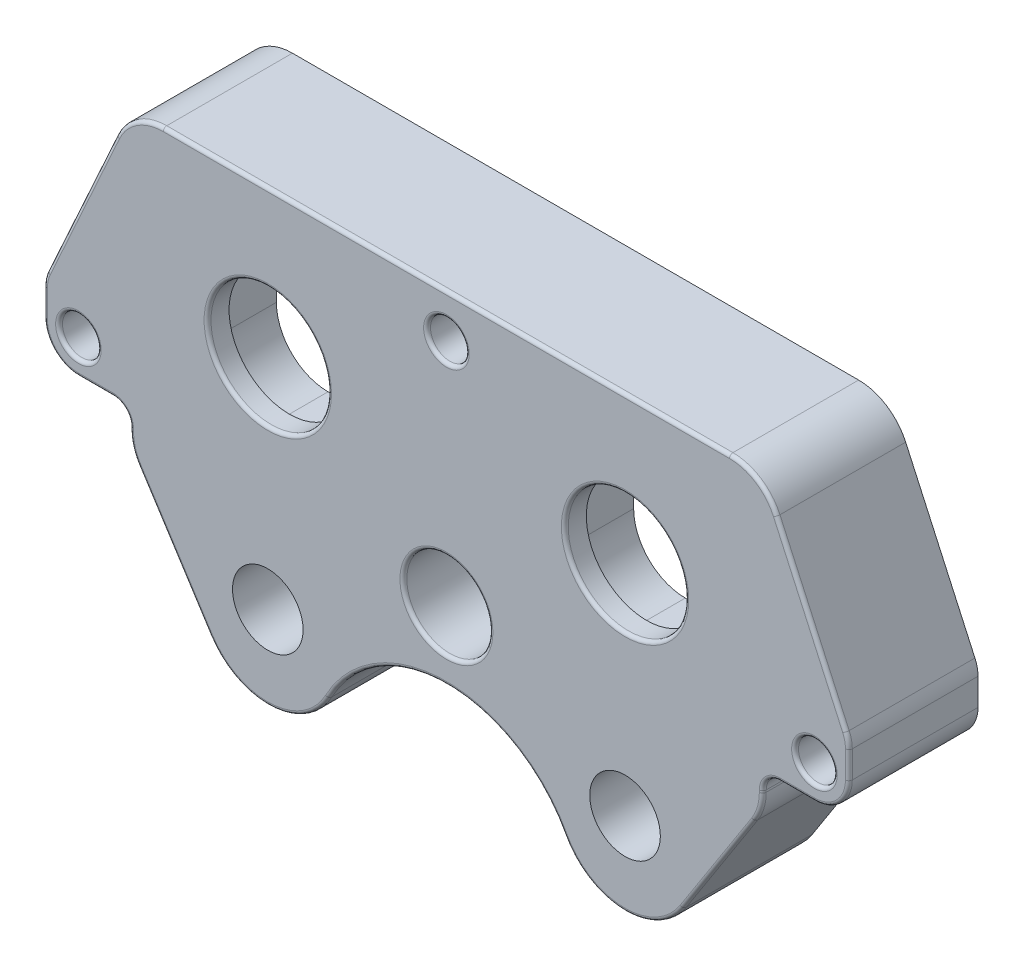
SolidWorks part; units mm, degrees
ref_plane "Front Plane" through (0, 0, 0) normal (0, 0, 1) x (1, 0, 0)
ref_plane "Top Plane" through (0, 0, 0) normal (0, 1, 0) x (1, 0, 0)
ref_plane "Right Plane" through (0, 0, 0) normal (1, 0, 0) x (0, 0, -1)
sketch "Sketch1" plane through (0, 0, 0) normal (0, 0, 1) x (1, 0, 0)
  line L0 (55.5, 15) -> (27.5, 15)
  line L1 (14, 15) -> (-14, 15)
  line L2 (14, 15) -> (14, -15)
  line L3 (14, -15) -> (-14, -15)
  line L4 (-14, 15) -> (-14, -15)
  line L5 (14, 15) -> (-14, -15) construction
  line L6 (14, -15) -> (-14, 15) construction
  line L7 (-16.75, -42) -> (16.75, -42)
  line L8 (-16.75, -42) -> (-16.75, 16)
  line L9 (-16.75, 16) -> (16.75, 16)
  line L10 (16.75, -42) -> (16.75, 16)
  line L11 (55.5, 15) -> (55.5, -15)
  line L12 (55.5, -15) -> (27.5, -15)
  line L13 (27.5, 15) -> (27.5, -15)
  line L14 (55.5, 15) -> (27.5, -15) construction
  line L15 (55.5, -15) -> (27.5, 15) construction
  line L16 (24.75, -42) -> (58.25, -42)
  line L17 (24.75, -42) -> (24.75, 16)
  line L18 (24.75, 16) -> (58.25, 16)
  line L19 (58.25, -42) -> (58.25, 16)
  circle A0 centre (0, 0) radius 19.05 construction
  circle A1 centre (41.5, 0) radius 19.05 construction
  circle A2 centre (20.75, -14.6491) radius 6.35 construction
  circle A3 centre (20.75, -14.6491) radius 41.275 construction
  circle A4 centre (0, 0) radius 7
  circle A5 centre (41.5, 0) radius 7
  circle A6 centre (0, -25.4) radius 4.3
  circle A7 centre (0, -27.1) radius 6.75
  circle A8 centre (41.5, -27.1) radius 6.75
  circle A9 centre (41.5, -25.4) radius 4.3
  point P0 (0, 0)
  point P10 (41.5, 0)
  point P11 (0, -42)
  point P22 (41.5, -42)
  dimension "D6" = 38.1
  dimension "D12" = 38.1
  dimension "D13" = 12.7
  dimension "D15" = 82.55
  dimension "D20" = 14
  dimension "D21" = 14
  dimension "D16" = 8.6
  dimension "D18" = 13.5
  dimension "D1" = 33.5
  dimension "D2" = 28
  dimension "D3" = 30
  dimension "D4" = 16
  dimension "D5" = 58
  dimension "D7" = 33.5
  dimension "D8" = 28
  dimension "D9" = 30
  dimension "D10" = 16
  dimension "D11" = 58
  dimension "D14" = 8
  dimension "D17" = 10.4
  dimension "D19" = 1.7
sketch "Sketch5" plane through (0, 0, 0) normal (0, 0, 1) x (1, 0, 0)
  line L0 (55.5, 15) -> (27.5, -15) construction
  line L1 (14, 15) -> (-14, 15) construction
  line L2 (-16, 17) -> (57.5, 17)
  line L3 (-16, 17) -> (-16, -35.1)
  line L4 (-16, -35.1) -> (57.5, -35.1)
  line L5 (57.5, 17) -> (57.5, -35.1)
  line L6 (-14, 15) -> (-14, -15) construction
  line L7 (55.5, 15) -> (55.5, -15) construction
  line L8 (14, -15) -> (-14, -15) construction
  line L9 (-16, -17) -> (-6.7301, -31.425)
  line L10 (55.5, -15) -> (27.5, -15) construction
  line L11 (57.5, -17) -> (48.2301, -31.425)
  line L12 (-26, -5) -> (-16, 17)
  line L13 (-16, -5) -> (-26, -5)
  line L14 (-16, -5) -> (-16, -13)
  line L15 (-16, -13) -> (-26, -13)
  line L16 (-26, -5) -> (-26, -13)
  line L17 (57.5, -5) -> (67.5, -5)
  line L18 (57.5, -5) -> (57.5, -13)
  line L19 (57.5, -13) -> (67.5, -13)
  line L20 (67.5, -5) -> (67.5, -13)
  line L21 (57.5, 17) -> (67.5, -5)
  circle A0 centre (0, 0) radius 7
  circle A1 centre (41.5, 0) radius 7
  circle A2 centre (20.75, -14.6491) radius 5
  circle A3 centre (0, -25.4) radius 4.1
  circle A4 centre (41.5, -25.4) radius 4.1
  circle A5 centre (41.5, -27.1) radius 6.75
  circle A6 centre (0, -27.1) radius 6.75
  circle A7 centre (0, -27.1) radius 8
  circle A8 centre (41.5, -27.1) radius 8
  circle A9 centre (-22, -9) radius 2.25
  circle A10 centre (20.75, 12) radius 2.25
  circle A11 centre (63.5, -9) radius 2.25
  circle A12 centre (20.75, -38.1651) radius 15.5159
  point P32 (-16, -17)
  point P39 (57.5, -17)
  point P58 (20.75, -22.6491)
  dimension "D1" = 10
  dimension "D2" = 14
  dimension "D3" = 14
  dimension "D4" = 8.2
  dimension "D5" = 8
  dimension "D6" = 13.5
  dimension "D7" = 13.5
  dimension "D18" = 4.5
  dimension "D22" = 4.5
  dimension "D26" = 4.5
  dimension "D8" = 8
  dimension "D9" = 2
  dimension "D10" = 2
  dimension "D11" = 2
  dimension "D12" = 2
  dimension "D13" = 2
  dimension "D14" = 8
  dimension "D15" = 10
  dimension "D16" = 9
  dimension "D17" = 10
  dimension "D19" = 8
  dimension "D20" = 6
  dimension "D21" = 4
  dimension "D23" = 21
  dimension "D24" = 4
  dimension "D25" = 6
extrude "Boss-Extrude5" add sketch "Sketch5" against normal blind 15 contours A8 A5 | A7 A6 | A6 A3 | A5 A4 | A8 L11 L5 L2 L3 L9 A7 L4 A10 A2 A1 A0 | L13 L16 L15 L3 A9 | L20 L17 L5 L19 A11 | L13 L3 L12 | L21 L5 L17 region at (20.75, -3.0463, 0) region at (-19.3333, 2.3333, 0) region at (60.8333, 2.3333, 0) region at (-16.1281, -9, 0) region at (62.5, -5.1281, 0) region at (-2.19, -19.6411, 0) region at (45.2256, -33.9228, 0) region at (34.9409, -27.1, 0) region at (-6.5591, -27.1, 0)
extrude "Cut-Extrude1" cut sketch "Sketch1" along normal blind 12.5 from surface contours L1 L4 L3 L2 A4 | L0 L13 L12 L11 A5 region at (55.0896, 0, 0) region at (13.5896, 0, 0) starting at face at (20.75, -13.3043, -15)
extrude "Cut-Extrude2" cut sketch "Sketch5<3>" along normal blind 2 from surface contours A5 A4 | A6 A3 region at (34.9409, -27.1, 0) region at (-6.5591, -27.1, 0) starting at face at (0, 0, -15)
sketch "Sketch5<3>" plane through (0, 0, 0) normal (0, 0, 1) x (1, 0, 0) same geometry as "Sketch5"
fillet "Fillet1" radius 6 8 edges at (55.5, 15, -8.75) (55.5, -15, -8.75) (27.5, -15, -8.75) (27.5, 15, -8.75) (14, -15, -8.75) (-14, -15, -8.75) (-14, 15, -8.75) (14, 15, -8.75)
fillet "Fillet2" radius 4 4 edges at (-26, -5, -7.5) (-26, -13, -7.5) (67.5, -5, -7.5) (67.5, -13, -7.5)
fillet "Fillet3" radius 6 4 edges at (-16, -17, -7.5) (57.5, -17, -7.5) (-16, 17, -7.5) (57.5, 17, -7.5)
fillet "Fillet4" radius 2 2 edges at (-16, -13, -7.5) (57.5, -13, -7.5)
extrude "Boss-Extrude6" add sketch "Sketch5<4>" along normal blind 2.3 from surface contours A2 region at (20.75, -14.6491, 0) starting at face at (6.75, -27.1, -15)
sketch "Sketch5<4>" plane through (0, 0, 0) normal (0, 0, 1) x (1, 0, 0) same geometry as "Sketch5"
sketch "Sketch6" plane through (0, 0, 0) normal (0, 0, 1) x (1, 0, 0)
  line L1 (-18.3338, -9) -> (-20.1669, -5.825)
  line L2 (-20.1669, -5.825) -> (-23.8331, -5.825)
  line L3 (-23.8331, -5.825) -> (-25.6662, -9)
  line L4 (-25.6662, -9) -> (-23.8331, -12.175)
  line L5 (-23.8331, -12.175) -> (-20.1669, -12.175)
  line L6 (-20.1669, -12.175) -> (-18.3338, -9)
  line L7 (24.287, 11.0352) -> (23.354, 14.5807)
  line L8 (23.354, 14.5807) -> (19.817, 15.5455)
  line L9 (19.817, 15.5455) -> (17.213, 12.9648)
  line L10 (17.213, 12.9648) -> (18.146, 9.4193)
  line L11 (18.146, 9.4193) -> (21.683, 8.4545)
  line L12 (21.683, 8.4545) -> (24.287, 11.0352)
  line L13 (59.8338, -9) -> (61.6669, -12.175)
  line L14 (61.6669, -12.175) -> (65.3331, -12.175)
  line L15 (65.3331, -12.175) -> (67.1662, -9)
  line L16 (67.1662, -9) -> (65.3331, -5.825)
  line L17 (65.3331, -5.825) -> (61.6669, -5.825)
  line L18 (61.6669, -5.825) -> (59.8338, -9)
  circle A0 centre (-22, -9) radius 3.175 construction
  circle A1 centre (20.75, 12) radius 3.175 construction
  circle A2 centre (63.5, -9) radius 3.175 construction
  dimension "D1" = 6.35
  dimension "D2" = 6.35
  dimension "D3" = 6.35
fillet "Fillet5" radius 0.4 30 edges at (-15.3848, 16.0446, 0) (-21.6201, 4.6358, 0) (-25.9093, -5.0196, 0) (-26, -7.4332, 0) (-24.8284, -11.8284, 0) (-20, -13, 0) (-16.5858, -13.5858, 0) (-16, -15.1192, 0) (-15.757, -16.9286, 0) (-10.8889, -24.9535, 0) (0.325, -35.0934, 0) (20.75, -22.6491, 0) (41.175, -35.0934, 0) (52.3889, -24.9535, 0) (57.257, -16.9286, 0) (57.5, -15.1192, 0) (58.0858, -13.5858, 0) (61.5, -13, 0) (66.3284, -11.8284, 0) (67.5, -7.4332, 0) (67.4093, -5.0196, 0) (63.1201, 4.6358, 0) (56.8848, 16.0446, 0) (65.75, -9, 0) (48.5, 0, 0) (25.75, -14.6491, 0) (23, 12, 0) (7, 0, 0) (-19.75, -9, 0) (20.75, 17, 0)
